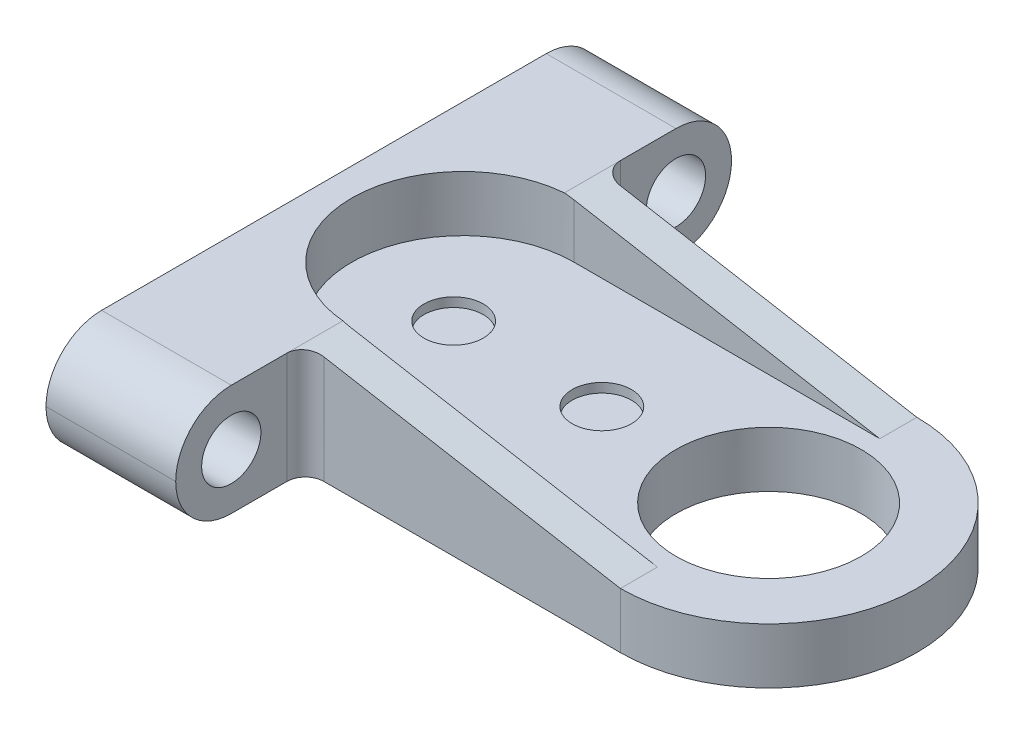
SolidWorks part; units mm, degrees
ref_plane "Front Plane" through (0, 0, 0) normal (0, 0, 1) x (1, 0, 0)
ref_plane "Top Plane" through (0, 0, 0) normal (0, 1, 0) x (1, 0, 0)
ref_plane "Right Plane" through (0, 0, 0) normal (1, 0, 0) x (0, 0, -1)
sketch "Sketch1" plane through (0, 0, 0) normal (0, 1, 0) x (1, 0, 0)
  line L0 (0, 8) -> (-17, 8)
  line L1 (-24, 15) -> (-17, 15)
  line L2 (-24, 15) -> (-24, -15)
  line L3 (-24, -15) -> (-17, -15)
  line L4 (-17, 15) -> (-17, 8)
  line L5 (0, -8) -> (-17, -8)
  line L6 (-17, -8) -> (-17, -15)
  circle A0 centre (0, 0) radius 5
  arc A1 (0, -8) -> (0, 8) centre (0, 0) ccw
  point P7 (-24, 0)
  dimension "D3" = 10
  dimension "D1" = 30
  dimension "D2" = 24
  dimension "D4" = 7
  dimension "D5" = 7
extrude "Boss-Extrude1" add sketch "Sketch1" along normal blind 6
fillet "Fillet1" radius 3 4 edges at (-20.5, 0, -15) (-20.5, 6, -15) (-20.5, 0, 15) (-20.5, 6, 15)
sketch "Sketch2" plane through (-24, 0, 0) normal (-1, 0, 0) x (0, 0, 1)
  circle A0 centre (-12, 3) radius 1.6
  circle A1 centre (12, 3) radius 1.6
  arc A2 (-12, 6) -> (-15, 3) centre (-12, 3) ccw construction
  arc A3 (15, 3) -> (12, 6) centre (12, 3) ccw construction
  dimension "D1" = 3.2
extrude "Cut-Extrude1" cut sketch "Sketch2" against normal through all
sketch "Sketch3" plane through (0, 0, 0) normal (0, 0, 1) x (1, 0, 0)
  line L0 (-17, 6) -> (8, 6)
  line L1 (8, 6) -> (8, 3)
  line L2 (8, 3) -> (0, 3)
  line L3 (0, 3) -> (-17, 6)
  line L4 (0, 6) -> (0, 0) construction
  dimension "D1" = 3
extrude "Cut-Extrude2" cut sketch "Sketch3" against normal through all and the other way through all
sketch "Sketch4" plane through (0, 3, 0) normal (0, 1, 0) x (1, 0, 0)
  line L0 (0, 0) -> (-16.5, 0) construction
  line L1 (0, -6) -> (-16.5, -6)
  line L2 (0, 6) -> (-16.5, 6)
  line L4 (-24, 12) -> (-24, -12) construction
  arc A0 (0, -6) -> (0, 6) centre (0, 0) ccw
  arc A2 (-16.5, 6) -> (-16.5, -6) centre (-16.5, 0) ccw
  point P3 (-8.25, 0)
  dimension "D1" = 12
  dimension "D2" = 1.5
extrude "Cut-Extrude3" cut sketch "Sketch4" along normal through all
fillet "Fillet3" radius 1 2 edges at (-17, 3, -8) (-17, 3, 8)
sketch "Sketch5" plane through (0, 3, 0) normal (0, 1, 0) x (1, 0, 0)
  line L0 (0, 0) -> (-9, 0) construction
  line L1 (-9, 0) -> (-17, 0) construction
  circle A0 centre (-9, 0) radius 1.6
  circle A1 centre (-17, 0) radius 1.6
  dimension "D3" = 3.2
  dimension "D1" = 9
  dimension "D2" = 8
extrude "Cut-Extrude4" cut sketch "Sketch5" against normal through all
sketch "Sketch6" plane through (0, 0, 0) normal (0, -1, 0) x (1, 0, 0)
  circle A0 centre (-17, 0) radius 3
  circle A1 centre (-9, 0) radius 3
  dimension "D1" = 6
extrude "Cut-Extrude5" cut sketch "Sketch6" against normal blind 2
sketch "Sketch7" plane through (0, 2, 0) normal (0, -1, 0) x (1, 0, 0)
  circle A0 centre (-17, 0) radius 1.6 construction
  circle A1 centre (-9, 0) radius 1.6 construction
  circle A2 centre (-17, 0) radius 1.6
  circle A3 centre (-9, 0) radius 1.6
extrude "Boss-Extrude2" add sketch "Sketch7" against normal blind 0.5
